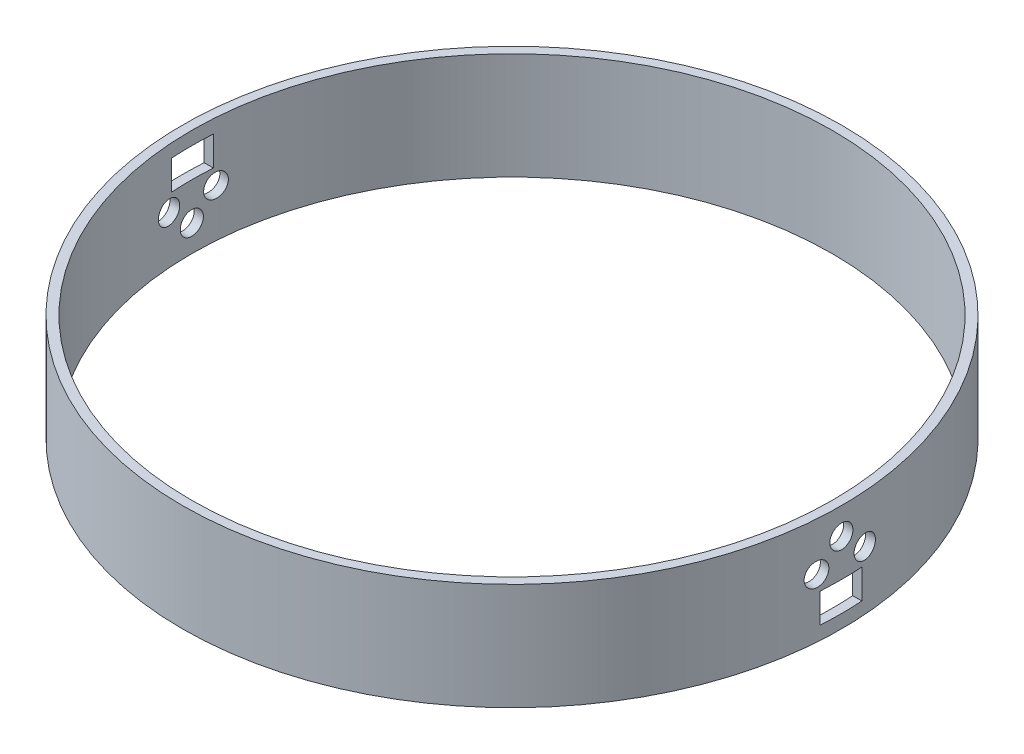
SolidWorks part; units mm, degrees
material "A-Glass Fiber"
ref_plane "Front Plane" through (0, 0, 0) normal (0, 0, 1) x (1, 0, 0)
ref_plane "Top Plane" through (0, 0, 0) normal (0, 1, 0) x (1, 0, 0)
ref_plane "Right Plane" through (0, 0, 0) normal (1, 0, 0) x (0, 0, -1)
sketch "Sketch1" plane through (0, 0, 0) normal (0, 1, 0) x (1, 0, 0)
  circle A0 centre (0, 0) radius 78.359
  circle A1 centre (0, 0) radius 76.1746
  dimension "D1" = 156.718
  dimension "D2" = 152.3492
extrude "Boss-Extrude1" add sketch "Sketch1" along normal blind 25.4
sketch "Sketch2" plane through (0, 0, 0) normal (1, 0, 0) x (0, 0, -1)
  line L0 (-78.359, 0) -> (78.359, 0) construction
  line L1 (-5, 3.175) -> (5, 3.175)
  line L2 (-5, 3.175) -> (-5, 10.175)
  line L3 (-5, 10.175) -> (5, 10.175)
  line L4 (5, 3.175) -> (5, 10.175)
  line L5 (-5, 3.175) -> (5, 10.175) construction
  line L6 (-5, 10.175) -> (5, 3.175) construction
  circle A0 centre (0, 19.065) radius 2.75
  point P0 (0, 6.675)
  dimension "D4" = 5.5
  dimension "D1" = 10
  dimension "D2" = 7
  dimension "D3" = 3.175
  dimension "D5" = 8.89
extrude "Cut-Extrude1" cut sketch "Sketch2" along normal through all
ref_plane "Plane1" through (0, 0, 0) normal (0.9973, 0, 0.0728) x (0, -1, 0)
sketch "Sketch5" plane through (0, 0, 0) normal (0.9973, 0, 0.0728) x (0, -1, 0)
  line L0 (-10.175, 0.7076) -> (-10.175, 10.681) construction
  circle A0 centre (-13.985, 0) radius 2.75
  point P2 (-6.7748, 14.6963)
  point P3 (-12.1689, 18.5515)
  point P4 (-10.8652, 15.3633)
  point P5 (-9.2057, 0)
  point P7 (0, 16.5419)
  point P10 (-11.831, 0)
  point P11 (0, 0)
  point P12 (-14.121, 0)
  dimension "D1" = 5.5
  dimension "D2" = 3.81
extrude "Cut-Extrude2" cut sketch "Sketch5" along normal through all
pattern_circular "CirPattern1" count 2 every 8.407 about axis through (0, 25.4, 0) along (0, 1, 0) of "Cut-Extrude2"
sketch "Sketch8" plane through (0, 0, 0) normal (1, 0, 0) x (0, 0, -1)
  line L0 (0, 25.4) -> (0, 0) construction
  line L1 (5, 15.225) -> (-5, 15.225)
  line L2 (5, 15.225) -> (5, 22.225)
  line L3 (5, 22.225) -> (-5, 22.225)
  line L4 (-5, 15.225) -> (-5, 22.225)
  line L5 (5, 15.225) -> (-5, 22.225) construction
  line L6 (5, 22.225) -> (-5, 15.225) construction
  line L8 (78.359, 25.4) -> (-78.359, 25.4) construction
  circle A0 centre (0, 6.335) radius 2.75
  point P0 (0, 18.725)
  point P7 (0, 32.5462)
  point P8 (0, 7.1997)
  point P11 (0, 17.8229)
  dimension "D4" = 5.5
  dimension "D3" = 3.175
  dimension "D5" = 8.89
  dimension "D1" = 10
  dimension "D2" = 7
extrude "Cut-Extrude3" cut sketch "Sketch8" against normal through all
sketch "Sketch9" plane through (0, 0, 0) normal (0.9973, 0, 0.0728) x (0, -1, 0)
  line L0 (-15.225, -0.7076) -> (-15.225, -10.681) construction
  line L1 (-25.4, 0) -> (0, 0) construction
  circle A0 centre (-11.415, 0) radius 2.75
  point P4 (-11.415, 0)
  dimension "D1" = 5.5
  dimension "D2" = 3.81
extrude "Cut-Extrude4" cut sketch "Sketch9" against normal through all
pattern_circular "CirPattern2" count 2 every 8.41 about axis through (0, 25.4, 0) along (0, 1, 0) of "Cut-Extrude4"
equation "\"Mid_Tube_Length\" = 1in"
equation "\"Bodytube_OD\" = 6.17in"
equation "\"Bodytube_ID\" = 5.998in"
equation "\"D1@Sketch1\"=\"Bodytube_OD\""
equation "\"D2@Sketch1\"= \"Bodytube_ID\""
equation "\"Camera_Cutout_Width\"=10mm"
equation "\"Camera_Cutout_Height\"=7mm"
equation "\"Fwd_Tube_Length\" = 40in"
equation "\"BKHD_Screw_Diam\"= 3.5mm"
equation "\"Fwd_BKHD_From_Top\" = 18in"
equation "\"Shear_Screw_Diameter\" = 0.086in"
equation "\"Shear_Screw_Coupler_Location\" = 4.5in"
equation "\"Motor_OD\" = 4in"
equation "\"Mid_Coupler_Length\" = 13in"
equation "\"Aft_Section_Length\"= 39in"
equation "\"AB_Coupler_OD_Length\"= 1in"
equation "\"AB_Coupling_Section_Length\"= 0.375in"
equation "\"AB_Coupler_Length\"= \"AB_Coupler_OD_Length\" + \"AB_Coupling_Section_Length\" * 2"
equation "\"Cutout_Angle\" = 80"
equation "\"AB_Paddle_Height\" = 0.375in"
equation "\"AB_Coupler_Num_Screws\"= 4"
equation "\"AB_BKHD_Thickness\" = 0.375in"
equation "\"AB_Mount_From_Bottom\" = 23.175in"
equation "\"Num_Cutouts\" = 3"
equation "\"AB_Coupler_OD\"= 6.17in"
equation "\"AB_Coupler_ID\"= 5.75in"
equation "\"AB_Coupler_Surface_Diameter\"= 5.998in"
equation "\"AB_Coupling_Screw_Diameter\"= 0.15748in"
equation "\"AB_Central_Bushing_Length\" = .4724in"
equation "\"Lead_Screw_Dist\" = 3.4in"
equation "\"Lead_Screw_Diam\" = 0.386in"
equation "\"Lead_Screw_Length\" = (\"Mid_Coupler_Length\" + 2*0.375in + 2*0.5in)"
equation "\"Paddle_Pin_Offset\" = .25in"
equation "\"Paddle_Pin_Radius\" = 2.25in"
equation "\"SS_Paddle_Pin_Radius\" = 2.25*0.66in"
equation "\"Paddle_Gear_OD\" = 3.2in"
equation "\"Drive_Gear_OD\" = 1.7in"
equation "\"Fin_Thickness\"= .118in"
equation "\"Guiderail_Cutout_Diameter\"= 1.5in"
equation "\"DB9_Hole_Dist\" = 25mm"
equation "\"DB9_Relief_Width\" = 0.47in"
equation "\"DB9_Relief_Hole_Offset\" = 0.09in"
equation "\"Airbrakes_Wire_Hole_Dia\" = .25in"
equation "\"Airbrakes_Wire_Hole_Dist\" = 1.1in"
equation "\"Servo_Gear_Offset\" = 0.5in"
equation "\"FWD_Shear_Screw_Dist\" = 1.5in"
equation "\"D2@Sketch2\"=\"Camera_Cutout_Height\""
equation "\"D1@Sketch2\"=\"Camera_Cutout_Width\""
equation "\"Camera_Screw_Dia\"=0.216535"
equation "\"D4@Sketch2\"=\"Camera_Screw_Dia\""
equation "\"D1@Sketch5\"=\"Camera_Screw_Dia\""
equation "\"Camera_Hole_Angle\"= atn ( 2 / 3 * tan ( 12.5deg ) )"
equation "\"D2@CirPattern1\"=\"Camera_Hole_Angle\""
equation "\"D4@Sketch8\"=\"Camera_Screw_Dia\""
equation "\"D1@Sketch9\"=\"Camera_Screw_Dia\""
